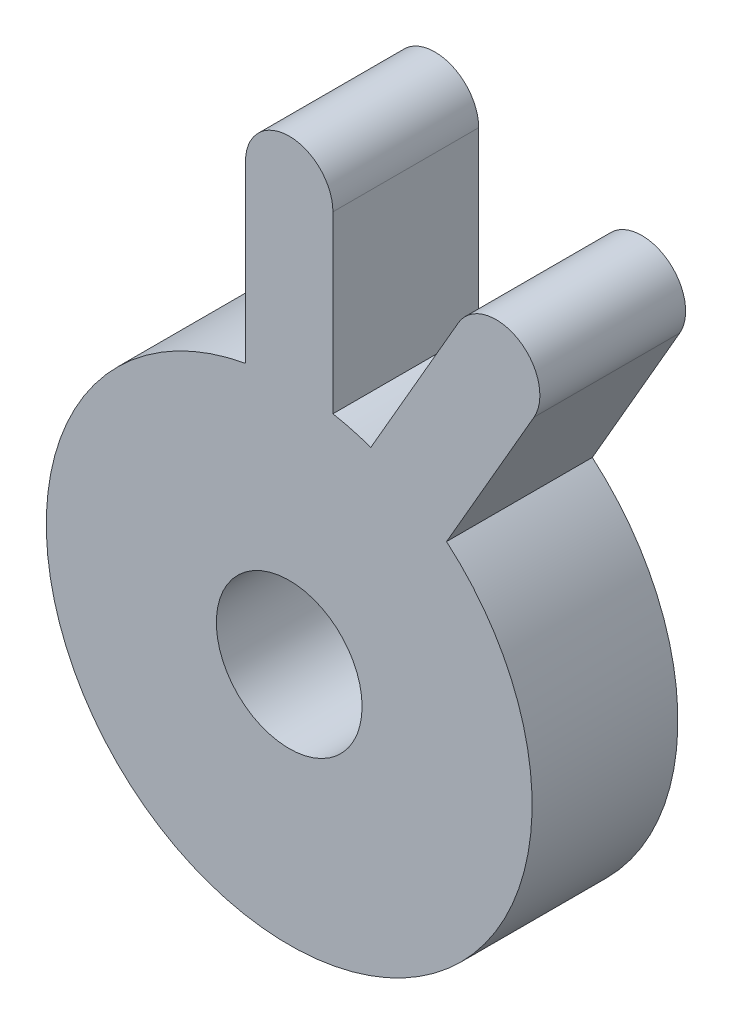
SolidWorks part; units mm, degrees
ref_plane "Front Plane" through (0, 0, 0) normal (0, 0, 1) x (1, 0, 0)
ref_plane "Top Plane" through (0, 0, 0) normal (0, 1, 0) x (1, 0, 0)
ref_plane "Right Plane" through (0, 0, 0) normal (1, 0, 0) x (0, 0, -1)
sketch "Sketch1" plane through (0, 0, 0) normal (0, 0, 1) x (1, 0, 0)
  line L0 (0, 0) -> (0, 51.188) construction
  line L1 (-4.5, 24.5917) -> (-4.5, 42.5917)
  line L2 (4.5, 24.5917) -> (4.5, 42.5917)
  line L3 (0, 0) -> (17.8221, 66.5129) construction
  line L4 (8.3987, 23.547) -> (17.3987, 39.1355)
  line L5 (16.1929, 19.047) -> (25.1929, 34.6355)
  line L6 (0, 0) -> (25.594, 44.3301) construction
  circle A0 centre (0, 0) radius 25
  circle A1 centre (0, 0) radius 7.5
  arc A2 (-4.5, 42.5917) -> (4.5, 42.5917) centre (0, 42.5917) cw
  arc A3 (25.1929, 34.6355) -> (17.3987, 39.1355) centre (21.2958, 36.8855) ccw
  circle A4 centre (0, 0) radius 34 construction
  dimension "D1" = 68
  dimension "D2" = 50
  dimension "D3" = 15
  dimension "D4" = 18
  dimension "D5" = 9
  dimension "D6" = 15
extrude "Boss-Extrude1" add sketch "Sketch1" along normal blind 15 contours A0 A1 | A2 L1 A0 L2 | L5 A3 L4 A0 region at (0, 35.5185, 0) region at (0, 24.2929, 0) region at (17.7593, 30.7599, 0)
scale "Scale2" scale about origin uniform scaling yes scale factor 0.264706
